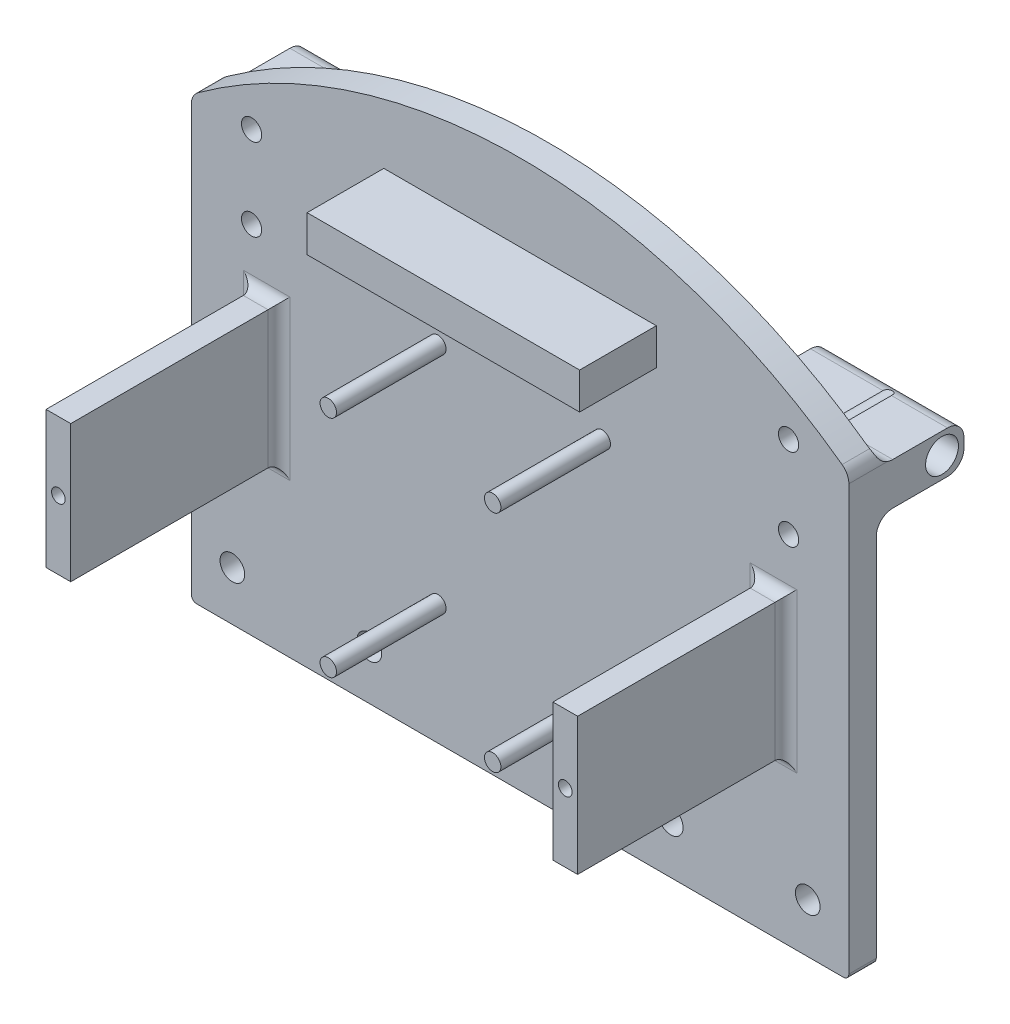
SolidWorks part; units mm, degrees
material "Cast Alloy Steel"
ref_plane "Front Plane" through (0, 0, 0) normal (0, 0, 1) x (1, 0, 0)
ref_plane "Top Plane" through (0, 0, 0) normal (0, 1, 0) x (1, 0, 0)
ref_plane "Right Plane" through (0, 0, 0) normal (1, 0, 0) x (0, 0, -1)
sketch "Sketch1" plane through (0, 0, 0) normal (0, 0, 1) x (1, 0, 0)
  line L0 (60, 0) -> (-60, 0)
  line L1 (0, 100) -> (0, 0) construction
  line L2 (-60, 0) -> (-60, 80)
  line L3 (60, 0) -> (60, 80)
  arc A0 (-60, 80) -> (60, 80) centre (0, 0) cw
  dimension "D2" = 100
  dimension "D3" = 80
  dimension "D1" = 60
extrude "Boss-Extrude1" add sketch "Sketch1" along normal mid plane 5
sketch "Sketch3" plane through (0, 0, 2.5) normal (0, 0, 1) x (1, 0, 0)
  line L1 (-60, 0) -> (60, 0) construction
  line L2 (0, 0) -> (0, 12.5) construction
  circle A0 centre (-52.5, 9) radius 2.25
  circle A1 centre (-27.5, 9) radius 2.25
  circle A2 centre (27.5, 9) radius 2.25
  circle A3 centre (52.5, 9) radius 2.25
  dimension "D4" = 4.5
  dimension "D1" = 25
  dimension "D2" = 27.5
  dimension "D3" = 9
extrude "Cut-Extrude1" cut sketch "Sketch3" against normal through all
sketch "Sketch4" plane through (0, 0, 2.5) normal (0, 0, 1) x (1, 0, 0)
  line L0 (0, 58.5011) -> (0, 27.5988) construction
  line L1 (-48.5, 55) -> (-44, 55)
  line L2 (-48.5, 55) -> (-48.5, 30)
  line L3 (-48.5, 30) -> (-44, 30)
  line L4 (-44, 55) -> (-44, 30)
  line L5 (-44, 42.5) -> (40.3264, 42.5) construction
  line L6 (44, 55) -> (44, 30)
  line L7 (48.5, 30) -> (44, 30)
  line L8 (48.5, 55) -> (48.5, 30)
  line L9 (48.5, 55) -> (44, 55)
  circle A0 centre (-15, 63) radius 1.5
  circle A1 centre (-15, 22) radius 1.5
  circle A2 centre (15, 22) radius 1.5
  circle A3 centre (15, 63) radius 1.5
  dimension "D6" = 3
  dimension "D1" = 44
  dimension "D2" = 4.5
  dimension "D3" = 25
  dimension "D4" = 30
  dimension "D5" = 63
  dimension "D7" = 15
extrude "Boss-Extrude2" add sketch "Sketch4" along normal blind 38 contours L8 L9 L6 L7 | L2 L3 L4 L1 region at (46.25, 42.5, 2.5)
fillet "Fillet2" radius 2 8 edges at (46.25, 55, 2.5) (44, 42.5, 2.5) (46.25, 30, 2.5) (48.5, 42.5, 2.5) (-46.25, 55, 2.5) (-44, 42.5, 2.5) (-46.25, 30, 2.5) (-48.5, 42.5, 2.5)
sketch "Sketch5" plane through (0, 0, 40.5) normal (0, 0, 1) x (1, 0, 0)
  line L0 (-46.25, 42.5) -> (46.25, 42.5) construction
  point P13 (0, 42.5)
hole_wizard "Tap Drill for M3x0.5 Tap1" positions "Sketch7" profile "Sketch6" hole size "M3x0.5" standard "ANSI Metric"
sketch "Sketch7" plane through (0, 0, 40.5) normal (0, 0, 1) x (1, 0, 0)
  point P0 (-46.25, 42.5)
  point P3 (46.25, 42.5)
sketch "Sketch6" plane through (-46.25, 42.5, 40.5) normal (1, 0, 0) x (0, -1, 0)
  line L0 (0, 0) -> (0, 15.7511)
  line L1 (0, 15.7511) -> (1.25, 15)
  line L2 (1.25, 15) -> (1.25, 0)
  line L5 (1.25, 0) -> (0, 0)
  line L10 (0, 15.7511) -> (-1.25, 15) construction
  line L11 (0, -6.35) -> (0, 107.95) construction
  dimension "Hole Dia." = 2.5
  dimension "Hole Depth" = 15
  dimension "Drill Angle" = 118
extrude "Boss-Extrude3" add sketch "Sketch4<3>" along normal blind 20 contours A1 | A2 | A0 | A3 region at (-15, 63, 2.5) region at (-15, 22, 2.5) region at (15, 22, 2.5) region at (15, 63, 2.5)
sketch "Sketch4<3>" plane through (0, 0, 2.5) normal (0, 0, 1) x (1, 0, 0) same geometry as "Sketch4"
sketch "Sketch8" plane through (60, 0, 0) normal (1, 0, 0) x (0, 0, -1)
  line L1 (-2.5, 0) -> (-2.5, 80) construction
  line L2 (2.5, 0) -> (2.5, 80) construction
  line L4 (-2.5, 70.6279) -> (-2.5, 78.3218)
  line L5 (0, 70.6279) -> (0, 78.3218) construction
  line L6 (-2.5, 70.6279) -> (18.5, 70.6279)
  line L7 (18.5, 70.6279) -> (18.5, 78.3218)
  line L8 (18.5, 78.3218) -> (-2.5, 78.3218)
  circle A2 centre (14.5, 74.4749) radius 3
  point P8 (0, 74.4749)
  dimension "D1" = 6
  dimension "D2" = 12
  dimension "D3" = 21
extrude "Boss-Extrude4" add sketch "Sketch8" against normal blind 25
fillet "Fillet3" radius 3 4 edges at (47.5, 78.3218, -18.5) (47.5, 78.3218, -2.5) (47.5, 70.6279, -2.5) (47.5, 70.6279, -18.5)
mirror "Mirror1" about plane through (0, 0, 0) normal (1, 0, 0) of "Fillet3", "Boss-Extrude4"
sketch "Sketch9" plane through (0, 0, 2.5) normal (0, 0, 1) x (1, 0, 0)
  line L1 (-24.8668, 79.2562) -> (24.8668, 79.2562)
  line L2 (-24.8668, 79.2562) -> (-24.8668, 85.9023)
  line L3 (-24.8668, 85.9023) -> (24.8668, 85.9023)
  line L4 (24.8668, 79.2562) -> (24.8668, 85.9023)
  line L5 (-24.8668, 79.2562) -> (24.8668, 85.9023) construction
  line L6 (-24.8668, 85.9023) -> (24.8668, 79.2562) construction
  point P0 (0, 82.5792)
extrude "Boss-Extrude5" add sketch "Sketch9" along normal blind 14
fillet "Fillet4" [suppressed] radius 3
fillet "Fillet5" radius 3 2 edges at (60, 80, -0.1535) (-60, 80, -0.1535)
fillet "Fillet6" radius 1 2 edges at (60, 0, 0) (-60, 0, 0)
sketch "Sketch10" plane through (0, 0, 2.5) normal (0, 0, 1) x (1, 0, 0)
  line L0 (0, 0) -> (0, 26.2657) construction
  line L1 (-59, 0) -> (59, 0) construction
  circle A0 centre (49, 80) radius 1.85
  circle A1 centre (49, 65) radius 1.85
  circle A2 centre (-49, 65) radius 1.85
  circle A3 centre (-49, 80) radius 1.85
  dimension "D1" = 3.7
  dimension "D2" = 15
  dimension "D3" = 49
  dimension "D4" = 65
extrude "Cut-Extrude2" cut sketch "Sketch10" against normal through all
